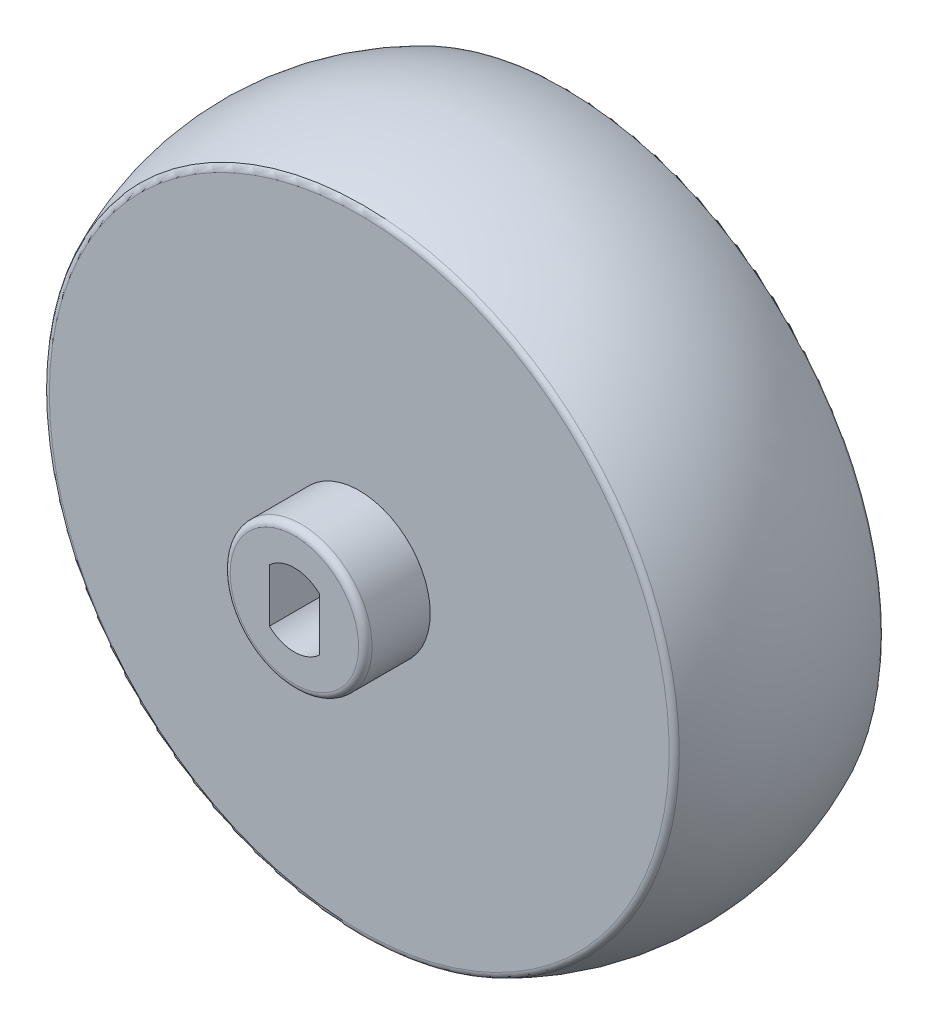
SolidWorks part; units mm, degrees
ref_plane "Front Plane" through (0, 0, 0) normal (0, 0, 1) x (1, 0, 0)
ref_plane "Top Plane" through (0, 0, 0) normal (0, 1, 0) x (1, 0, 0)
ref_plane "Right Plane" through (0, 0, 0) normal (1, 0, 0) x (0, 0, -1)
sketch "Sketch1" plane through (0, 0, 0) normal (1, 0, 0) x (0, 0, -1)
  line L0 (-18.6368, 0) -> (16.4545, 0) construction
  line L1 (-12.55, 0) -> (-12.55, 5.25)
  line L2 (-12.55, 5.25) -> (-7.75, 5.25)
  line L3 (-7.75, 5.25) -> (-7.75, 23.25)
  line L4 (-12.55, 0) -> (12.55, 0)
  line L11 (7.75, 23.25) -> (7.75, 5.25)
  line L12 (7.75, 5.25) -> (12.55, 5.25)
  line L13 (12.55, 5.25) -> (12.55, 0)
  arc A0 (7.75, 23.25) -> (-7.75, 23.25) centre (0, 6.9643) ccw
  point P5 (7.75, 14.25)
  point P10 (0, 25)
  dimension "D1" = 15.5
  dimension "D2" = 4.8
  dimension "D3" = 10.5
  dimension "D4" = 50
  dimension "D5" = 1.75
revolve "Revolve1" add sketch "Sketch1" angle 360 about L0
sketch "Sketch2" plane through (0, 0, 0) normal (1, 0, 0) x (0, 0, -1)
  line L0 (-16.3933, 0) -> (18.8041, 0) construction
  line L1 (12.55, 0) -> (12.55, 2.75)
  line L2 (12.55, -5.25) -> (12.55, 5.25) construction
  line L3 (12.55, 2.75) -> (7.75, 2.75)
  line L4 (7.75, 2.75) -> (7.75, 1.5)
  line L5 (7.75, 1.5) -> (-0.85, 1.5)
  line L6 (-0.85, 1.5) -> (-0.85, 0)
  line L7 (7.75, -5.25) -> (7.75, 5.25) construction
  line L8 (-12.55, 5.25) -> (-12.55, -5.25) construction
  line L9 (12.55, 0) -> (-0.85, 0)
  dimension "D1" = 5.5
  dimension "D2" = 3
  dimension "D3" = 11.7
revolve "Cut-Revolve1" cut sketch "Sketch2" angle 360 about L0
sketch "Sketch3" plane through (0, 0, 12.55) normal (0, 0, 1) x (1, 0, 0)
  line L0 (-1.85, -1.9666) -> (-1.85, 1.9666)
  line L1 (1.85, 1.9666) -> (1.85, -1.9666)
  arc A0 (1.85, 1.9666) -> (-1.85, 1.9666) centre (0, 0) ccw
  arc A1 (1.85, -1.9666) -> (-1.85, -1.9666) centre (0, 0) cw
  point P6 (1.85, 0)
  point P8 (-1.85, 0)
  dimension "D2" = 2.7
  dimension "D3" = 2.7
  dimension "D1" = 3.7
extrude "Cut-Extrude1" cut sketch "Sketch3" against normal up to surface (11.7 mm away) up to face at (1.5, 0, 0.85)
fillet "Fillet1" radius 0.5 4 edges at (23.25, 0, 7.75) (23.25, 0, -7.75) (5.25, 0, 12.55) (5.25, 0, -12.55)
ref_axis "Axis1" through (0, 0, -41.4948) along (0, 0, 1)
